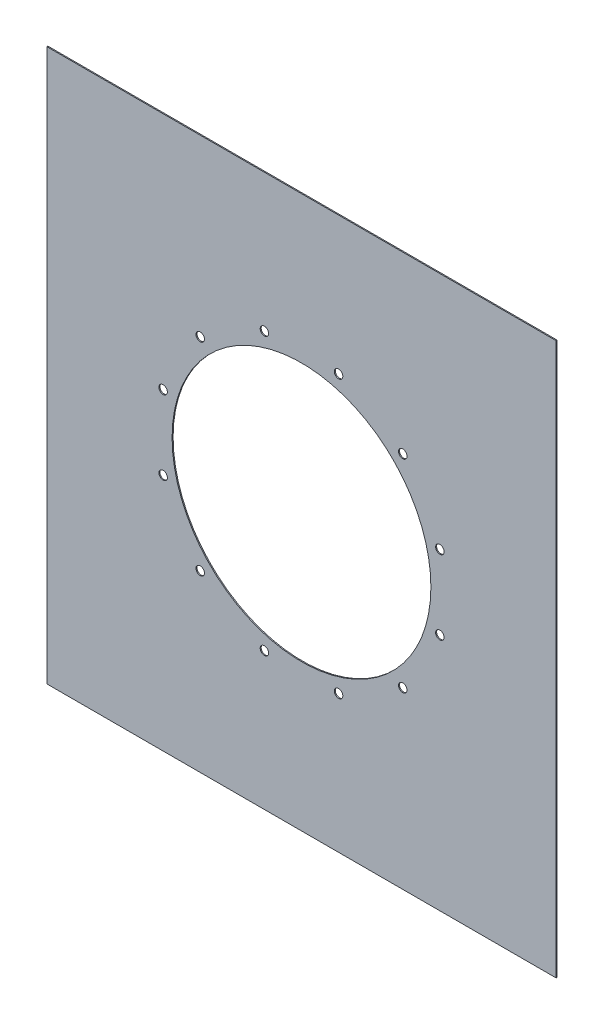
SolidWorks part; units mm, degrees
material "AISI 304"
ref_plane "Front Plane" through (0, 0, 0) normal (0, 0, 1) x (1, 0, 0)
ref_plane "Top Plane" through (0, 0, 0) normal (0, 1, 0) x (1, 0, 0)
ref_plane "Right Plane" through (0, 0, 0) normal (1, 0, 0) x (0, 0, -1)
sketch "Sketch1" plane through (0, 0, 0) normal (0, 0, 1) x (1, 0, 0)
  line L0 (152.4, 0) -> (185, 0) construction
  line L1 (300, -325) -> (-300, -325)
  line L2 (300, -325) -> (300, 325)
  line L3 (300, 325) -> (-300, 325)
  line L4 (-300, -325) -> (-300, 325)
  line L5 (300, -325) -> (-300, 325) construction
  line L6 (300, 325) -> (-300, -325) construction
  line L7 (-43.6628, 162.9517) -> (43.6628, 162.9517) construction
  line L8 (0, 0) -> (0, 162.9517) construction
  circle A0 centre (0, 0) radius 152.4
  circle A1 centre (0, 0) radius 185 construction
  circle A3 centre (0, 0) radius 168.7 construction
  circle A4 centre (43.6628, 162.9517) radius 5
  circle A5 centre (119.2889, 119.2889) radius 5
  circle A6 centre (162.9517, 43.6628) radius 5
  circle A7 centre (162.9517, -43.6628) radius 5
  circle A8 centre (119.2889, -119.2889) radius 5
  circle A9 centre (43.6628, -162.9517) radius 5
  circle A10 centre (-43.6628, -162.9517) radius 5
  circle A11 centre (-119.2889, -119.2889) radius 5
  circle A12 centre (-162.9517, -43.6628) radius 5
  circle A13 centre (-162.9517, 43.6628) radius 5
  circle A14 centre (-119.2889, 119.2889) radius 5
  circle A15 centre (-43.6628, 162.9517) radius 5
  point P0 (0, 0)
  point P12 (168.7, 0)
  point P15 (0, 0)
  point P40 (0, 0)
  dimension "D3" = 304.8
  dimension "D4" = 370
  dimension "D5" = 10
  dimension "D1" = 650
  dimension "D2" = 600
  dimension "D6" = 12
base flange "Base-Flange1" sketch "Sketch1" thickness 1.2 reverse thickness direction no parameters "D1"=0.7366
sketch "Bend-Lines1" [suppressed] plane through (0, 0, 0) normal (0, 1, 0) x (1, 0, 0)
sketch "Bounding-Box1" [suppressed] plane through (0, 0, 0) normal (0, 1, 0) x (1, 0, 0)
sheet metal parameters "Sheet-Metal1" thickness 1.2 parameters "D1"=0.7366
flat pattern "Flat-Pattern1" [suppressed]
sketch "Bend-Lines2" plane through (0, 0, 0) normal (0, 1, 0) x (1, 0, 0)
sketch3d "Bounding-Box2" [suppressed]
  line L0 (-300, 325, 0) -> (-300, -325, 0) construction
  line L1 (300, 325, 0) -> (300, -325, 0) construction
  line L2 (-300, 325, 0) -> (300, 325, 0) construction
  line L3 (-300, -325, 0) -> (300, -325, 0) construction
